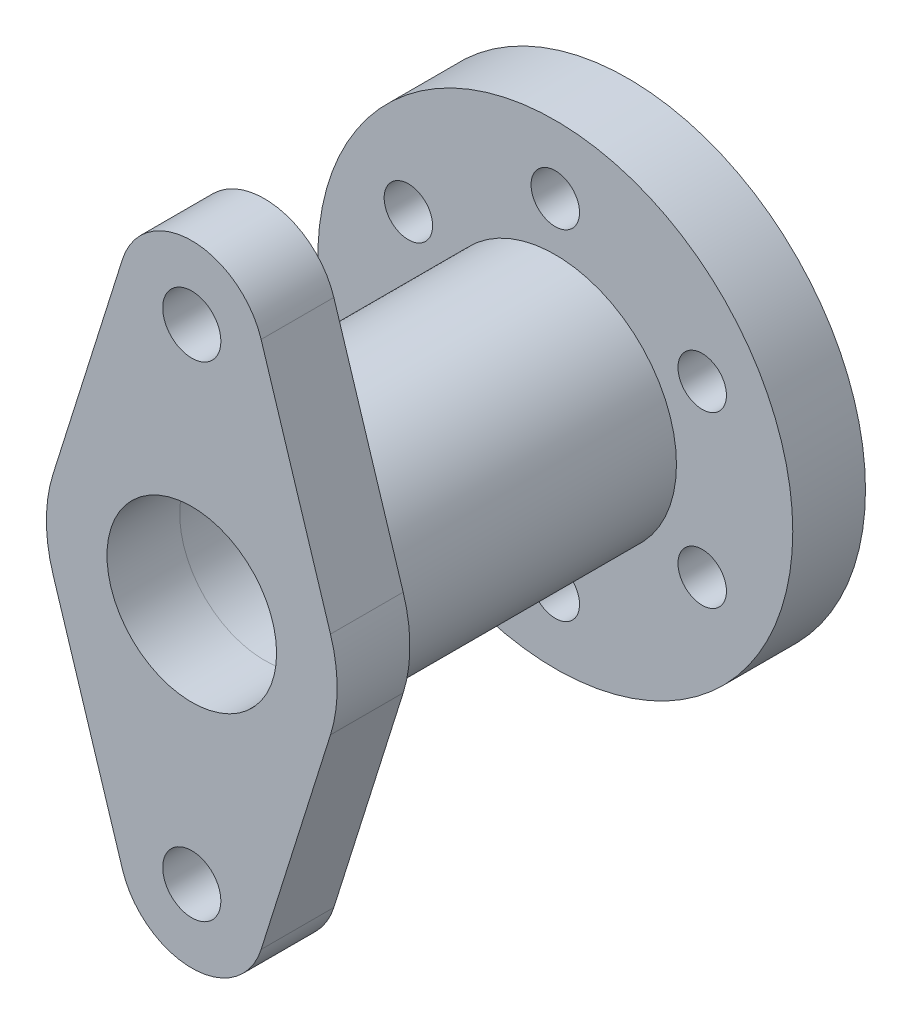
SolidWorks part; units mm, degrees
material "1350 Alloy"
ref_plane "Front Plane" through (0, 0, 0) normal (0, 0, 1) x (1, 0, 0)
ref_plane "Top Plane" through (0, 0, 0) normal (0, 1, 0) x (1, 0, 0)
ref_plane "Right Plane" through (0, 0, 0) normal (1, 0, 0) x (0, 0, -1)
sketch "Sketch1" plane through (0, 0, 0) normal (0, 0, 1) x (1, 0, 0)
  line L0 (0, 0) -> (0, 35) construction
  circle A0 centre (0, 0) radius 49
  circle A1 centre (0, 0) radius 35 construction
  circle A2 centre (0, 0) radius 25
  circle A3 centre (0, 35) radius 5
  circle A4 centre (30.3109, 17.5) radius 5
  circle A5 centre (30.3109, -17.5) radius 5
  circle A6 centre (0, -35) radius 5
  circle A7 centre (-30.3109, -17.5) radius 5
  circle A8 centre (-30.3109, 17.5) radius 5
  point P20 (0, 0)
  dimension "D1" = 98
  dimension "D2" = 70
  dimension "D3" = 50
  dimension "D4" = 10
  dimension "D5" = 6
extrude "Boss-Extrude1" add sketch "Sketch1" against normal blind 15 contours A2 | A0 A8 A7 A6 A5 A4 A3 A2 region at (-47.6141, 0, 0) region at (0, 0, 0)
extrude "Boss-Extrude2" add sketch "Sketch1<3>" along normal blind 60 contours A2
sketch "Sketch1<3>" plane through (0, 0, 0) normal (0, 0, 1) x (1, 0, 0) same geometry as "Sketch1"
sketch "Sketch2" plane through (0, 0, 60) normal (0, 0, 1) x (1, 0, 0)
  line L0 (0, 0) -> (0, 50) construction
  line L1 (0, 50) -> (0, -50) construction
  line L2 (-14.3091, 54.5) -> (-28.6182, 9)
  line L3 (14.3091, 54.5) -> (28.6182, 9)
  line L4 (-37.6442, 0) -> (34.5808, 0) construction
  line L5 (-14.3091, -54.5) -> (-28.6182, -9)
  line L6 (14.3091, -54.5) -> (28.6182, -9)
  circle A0 centre (0, 50) radius 15
  circle A1 centre (0, -50) radius 15
  circle A2 centre (0, 50) radius 6
  circle A3 centre (0, -50) radius 6
  arc A4 (-28.6182, 9) -> (-28.6182, -9) centre (0, 0) ccw
  arc A5 (28.6182, -9) -> (28.6182, 9) centre (0, 0) ccw
  circle M2 centre (0, 0) radius 25
  dimension "D1" = 30
  dimension "D3" = 30
  dimension "D4" = 12
  dimension "D5" = 12
  dimension "D6" = 60
  dimension "D2" = 100
extrude "Boss-Extrude3" add sketch "Sketch2" along normal blind 15 separate body contours L6 A5 L3 A0 L2 A4 L5 A1 M2 | A1 A3 | A0 A2 | M2 region at (-2.4652, 33.9439, 60) region at (0, 64.5757, 60) region at (-2.212, -35.5931, 60) region at (0, 0, 60)
sketch "Sketch3" plane through (0, 0, 75) normal (0, 0, 1) x (1, 0, 0)
  line L0 (0, 0) -> (-37.0603, 0) construction
  line L1 (-37.0603, 0) -> (52.7728, 0) construction
  circle A0 centre (0, 0) radius 17.5
  dimension "D1" = 35
extrude "Cut-Extrude1" cut sketch "Sketch3" against normal blind 30
sketch "Sketch4" plane through (0, 0, 45) normal (0, 0, 1) x (1, 0, 0)
  circle A2 centre (0, 0) radius 14
  dimension "D1" = 28
extrude "Cut-Extrude2" cut sketch "Sketch4" against normal through all
